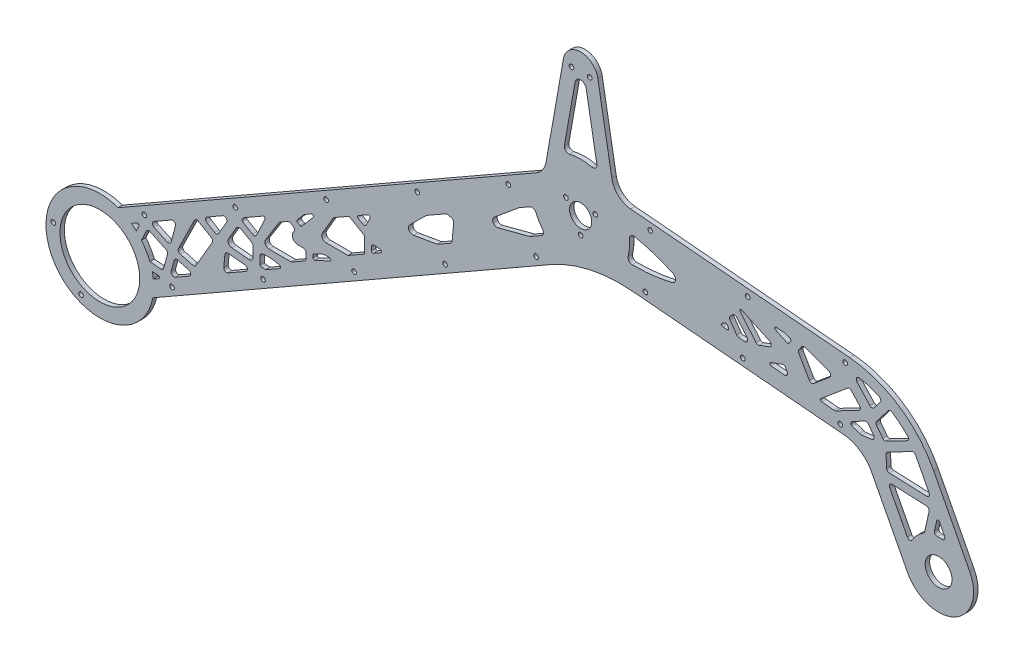
SolidWorks part; units mm, degrees
material "6061-T6 (SS)"
ref_plane "Front Plane" through (0, 0, 0) normal (0, 0, 1) x (1, 0, 0)
ref_plane "Top Plane" through (0, 0, 0) normal (0, 1, 0) x (1, 0, 0)
ref_plane "Right Plane" through (0, 0, 0) normal (1, 0, 0) x (0, 0, -1)
sketch "Reference Sketch" plane through (0, 0, 0) normal (0, 0, 1) x (1, 0, 0)
  line L0 (-343.92, -196.825) -> (0, 0) construction
  line L1 (-243.92, 103.175) -> (356.08, 103.175) construction
  line L2 (-243.92, 103.175) -> (-243.92, 0) construction
  line L3 (-243.92, 0) -> (356.08, 0) construction
  line L4 (356.08, 103.175) -> (356.08, 0) construction
  line L5 (0, 0) -> (256.08, -92.7116) construction
  line L6 (256.08, -92.7116) -> (56.08, -196.825) construction
  line L7 (256.08, -92.7116) -> (456.08, -196.825) construction
  line L8 (-343.92, -196.825) -> (56.08, -196.825) construction
  line L9 (56.08, -196.825) -> (456.08, -196.825) construction
  circle A1 centre (-343.92, -196.825) radius 100 construction
  circle A2 centre (56.08, -196.825) radius 100 construction
  circle A3 centre (456.08, -196.825) radius 100 construction
  circle A4 centre (-343.92, -196.825) radius 16.05 construction
  circle A5 centre (-343.92, -196.825) radius 28.55 construction
  circle A6 centre (-343.92, -196.825) radius 38.55 construction
  circle A7 centre (-343.92, -196.825) radius 33.55 construction
  point P13 (-343.92, -296.825)
  point P14 (556.08, -196.825)
  point P17 (-443.92, -196.825)
  dimension "D3" = 32.1
  dimension "D5" = 200
  dimension "D9" = 57.1
  dimension "D10" = 10
  dimension "D11" = 5
  dimension "D1" = 600
  dimension "D2" = 103.175
  dimension "D4" = 243.92
  dimension "D6" = 125
  dimension "D7" = 400
  dimension "D8" = 1000
sketch "Sketch2" plane through (0, 0, 0) normal (0, 0, 1) x (1, 0, 0)
  line L0 (-379.7168, -188.5069) -> (-32.0065, 10.4873)
  line L1 (-354.8814, -231.9028) -> (-21.5627, -41.1449)
  line L2 (-343.92, -196.825) -> (0, 0) construction
  line L3 (-184.3777, -76.7146) -> (-159.5423, -120.1104) construction
  line L4 (-24.685, 20.9013) -> (-12.3101, 91.0831)
  line L5 (12.3101, 91.0831) -> (22.322, 34.3028)
  line L6 (0, 98.4125) -> (0, 112.7) construction
  line L7 (-5.4848, 79.4125) -> (5.4848, 79.4125) construction
  line L8 (5.4848, 79.4125) -> (10.9697, 88.9125) construction
  line L9 (10.9697, 88.9125) -> (5.4848, 98.4125) construction
  line L10 (5.4848, 98.4125) -> (-5.4848, 98.4125) construction
  line L11 (-5.4848, 98.4125) -> (-10.9697, 88.9125) construction
  line L12 (-10.9697, 88.9125) -> (-5.4848, 79.4125) construction
  line L13 (-243.92, 103.175) -> (356.08, 103.175) construction
  line L14 (0, 88.9125) -> (0, 0) construction
  line L15 (35.7868, 21.9646) -> (192.5861, 8.2464)
  line L16 (252.5753, -31.8371) -> (278.2553, -81.1679)
  line L17 (233.9047, -104.2553) -> (208.2247, -54.9245)
  line L18 (36.8237, -28.3172) -> (188.2284, -41.5633)
  line L19 (0, 0) -> (192.5861, -16.8491) construction
  line L21 (-365.6311, -190.9191) -> (-338.0141, -175.1139) construction
  line L22 (-381.5729, -195.33) -> (-361.7045, -230.0467)
  line L23 (256.08, -92.7116) -> (56.08, -196.825) construction
  line L25 (-243.92, 0) -> (356.08, 0) construction
  circle A0 centre (0, 0) radius 7.9375
  circle A1 centre (-343.92, -196.825) radius 16.05
  arc A3 (-12.3101, 91.0831) -> (12.3101, 91.0831) centre (0, 88.9125) cw
  circle A4 centre (0, 88.9125) radius 6.5 construction
  circle A5 centre (-6.5, 88.9125) radius 1.65
  circle A6 centre (6.5, 88.9125) radius 1.65
  circle A7 centre (0, 88.9125) radius 9.5 construction
  arc A8 (252.5753, -31.8371) -> (192.5861, 8.2464) centre (186.0495, -66.4682) ccw
  circle A9 centre (256.08, -92.7116) radius 9.5885
  arc A10 (278.2553, -81.1679) -> (233.9047, -104.2553) centre (256.08, -92.7116) cw
  arc A11 (-21.5627, -41.1449) -> (36.8237, -28.3172) centre (28.1082, -127.9366) cw
  arc A12 (188.2284, -41.5633) -> (208.2247, -54.9245) centre (186.0495, -66.4682) cw
  arc A13 (22.322, 34.3028) -> (35.7868, 21.9646) centre (37.0941, 36.9075) ccw
  arc A14 (-32.0065, 10.4873) -> (-24.685, 20.9013) centre (-39.4572, 23.506) ccw
  circle A17 centre (-343.92, -196.825) radius 22.5 construction
  circle A18 centre (-365.6311, -190.9191) radius 1.65
  circle A19 centre (-338.0141, -175.1139) radius 1.65
  circle A20 centre (-322.2089, -202.7309) radius 1.65
  circle A21 centre (-349.8259, -218.5361) radius 1.65
  arc A27 (-379.7168, -188.5069) -> (-381.5729, -195.33) centre (-377.2333, -192.8465) ccw
  arc A28 (-361.7045, -230.0467) -> (-354.8814, -231.9028) centre (-357.3649, -227.5632) ccw
  circle A29 centre (-343.92, -196.825) radius 33.55 construction
  circle A32 centre (-343.92, -196.825) radius 38.55 construction
  point P16 (-171.96, -98.4125)
  point P64 (-343.92, -196.825)
  dimension "D1" = 15.875
  dimension "D2" = 32.1
  dimension "D3" = 45
  dimension "D5" = 13
  dimension "D6" = 3.3
  dimension "D7" = 6
  dimension "D12" = 50
  dimension "D14" = 100
  dimension "D16" = 15
  dimension "D17" = 5
  dimension "D18" = 25
  dimension "D19" = 3.3
  dimension "D15" = 4
  dimension "D20" = 19.177
  dimension "D4" = 50
  dimension "D8" = 19
  dimension "D9" = 14.2875
  dimension "D10" = 9.525
  dimension "D11" = 10
  dimension "D13" = 50
extrude "Base" add sketch "Sketch2" along normal blind 3.175
sketch "Sketch3" plane through (0, 0, 3.175) normal (0, 0, 1) x (1, 0, 0)
  line L0 (-343.92, -196.825) -> (0, 0) construction
  line L5 (0, 0) -> (197.3986, -17.2701) construction
  line L6 (192.5861, 8.2464) -> (35.7868, 21.9646) construction
  line L9 (36.8237, -28.3172) -> (188.2284, -41.5633) construction
  line L10 (-31.8958, -41.2976) -> (0, 0) construction
  line L11 (0, 0) -> (46.2693, -24.1244) construction
  circle A0 centre (-357.3649, -227.5632) radius 1.65
  circle A1 centre (-343.92, -196.825) radius 33.55 construction
  arc A2 (-361.7045, -230.0467) -> (-354.8814, -231.9028) centre (-357.3649, -227.5632) ccw construction
  circle A3 centre (-292.2711, -190.3101) radius 1.65
  circle A4 centre (-227.1773, -153.057) radius 1.65
  circle A5 centre (-162.0835, -115.8038) radius 1.65
  circle A6 centre (-96.9897, -78.5507) radius 1.65
  circle A7 centre (-31.8958, -41.2976) radius 1.65
  circle A8 centre (-312.1394, -155.5934) radius 1.65
  circle A9 centre (-377.2333, -192.8465) radius 1.65
  circle A10 centre (-247.0456, -118.3403) radius 1.65
  circle A11 centre (-181.9518, -81.0871) radius 1.65
  circle A12 centre (-116.858, -43.834) radius 1.65
  circle A13 centre (-51.7642, -6.5809) radius 1.65
  circle A14 centre (46.2693, -24.1244) radius 1.65
  circle A15 centre (116.0029, -30.2253) radius 1.65
  circle A16 centre (185.7366, -36.3262) radius 1.65
  circle A17 centre (189.2228, 3.5215) radius 1.65
  circle A18 centre (119.4892, 9.6224) radius 1.65
  circle A19 centre (49.7555, 15.7234) radius 1.65
  dimension "D1" = 3.3
  dimension "D2" = 6
  dimension "D3" = 5
  dimension "D5" = 3
  dimension "D4" = 75
  dimension "D6" = 70
extrude "Strut Holes" cut sketch "Sketch3" against normal through all
sketch "Sketch6" plane through (0, 0, 3.175) normal (0, 0, 1) x (1, 0, 0)
  line L0 (-315.2692, -197.7109) -> (-301.7593, -189.9792)
  line L1 (-354.8814, -231.9028) -> (-21.5627, -41.1449) construction
  line L2 (-289.845, -183.1607) -> (-279.9388, -177.4914)
  line L3 (-225.0683, -146.089) -> (-215.0659, -140.3647)
  line L4 (-202.4189, -105.5114) -> (-200.6862, -106.5205)
  line L5 (-330.4255, -170.6672) -> (-317.3783, -163.2003)
  line L6 (-32.0065, 10.4873) -> (-379.7168, -188.5069) construction
  line L7 (-315.9769, -164.4942) -> (-323.4022, -180.2613)
  line L8 (-325.3934, -181.4009) -> (-327.8261, -181.1787)
  line L9 (-302.165, -188.1154) -> (-317.5291, -186.7124)
  line L10 (-319.5204, -187.852) -> (-321.9207, -192.9489)
  line L11 (-295.5333, -171.6316) -> (-298.2962, -181.7883)
  line L12 (-300.4079, -183.2551) -> (-315.6625, -181.8621)
  line L13 (-317.2901, -179.0183) -> (-310.6415, -164.9005)
  line L14 (-307.9799, -163.9432) -> (-296.6111, -169.2972)
  line L15 (-280.4073, -173.8257) -> (-288.2923, -171.6808)
  line L16 (-290.7472, -173.0857) -> (-292.8686, -180.8843)
  line L17 (-292.7787, -149.122) -> (-305.2156, -156.2396)
  line L18 (-305.0743, -159.7848) -> (-295.766, -164.1685)
  line L19 (-292.984, -162.8841) -> (-289.8554, -151.3828)
  line L20 (-286.4122, -167.0105) -> (-277.4777, -169.4409)
  line L21 (-275.2245, -168.5176) -> (-263.487, -148.3649)
  line L22 (-264.2087, -145.6301) -> (-273.4911, -140.2238)
  line L23 (-276.2919, -141.0684) -> (-287.6814, -164.1971)
  line L24 (-267.3269, -134.556) -> (-255.9817, -128.0631)
  line L25 (-253.26, -130.8055) -> (-258.9575, -140.5878)
  line L26 (-261.6923, -141.3094) -> (-267.3401, -138.02)
  line L27 (-255.2613, -159.7424) -> (-254.4886, -151.2802)
  line L28 (-252.315, -149.4703) -> (-240.2297, -150.5739)
  line L29 (-292.2711, -190.3101) -> (-299.0066, -188.4038) construction
  line L30 (-252.2762, -161.6601) -> (-239.4181, -154.3014)
  line L31 (-246.5402, -131.1894) -> (-251.7948, -140.2114)
  line L32 (-249.4752, -144.7088) -> (-237.508, -145.8016)
  line L33 (-234.2352, -142.8254) -> (-234.2117, -136.6339)
  line L34 (-235.7018, -134.0302) -> (-242.4379, -130.1069)
  line L35 (-229.2226, -139.4963) -> (-229.2439, -145.1246)
  line L36 (-241.7536, -124.7193) -> (-234.6398, -128.8625)
  line L37 (-231.8238, -127.9864) -> (-225.7969, -115.1887)
  line L38 (-227.1983, -113.8948) -> (-240.4869, -121.4998)
  line L39 (-215.6688, -112.1749) -> (-225.38, -127.5855)
  line L40 (-222.8533, -132.1849) -> (-207.4544, -132.2434)
  line L41 (-206.4534, -131.9792) -> (-197.5057, -126.8584)
  line L42 (-196.4991, -125.1302) -> (-196.4845, -121.2849)
  line L43 (-198.4769, -119.2773) -> (-202.2607, -119.2629)
  line L44 (-205.6297, -113.1304) -> (-205.0269, -112.1739)
  line L45 (-205.7124, -109.3794) -> (-207.4618, -108.3605)
  line L46 (-209.4618, -108.3529) -> (-214.9702, -111.5053)
  line L47 (-223.2993, -137.1832) -> (-189.5978, -137.3112) construction
  line L48 (-199.4194, -106.3021) -> (-191.3609, -96.7721)
  line L49 (-192.6212, -95.2585) -> (-197.479, -98.0386)
  line L50 (-198.0128, -98.4831) -> (-202.6792, -104.0016)
  line L51 (-191.4798, -120.0542) -> (-191.4866, -121.8475)
  line L52 (-190.0674, -122.7592) -> (-179.2455, -117.7628)
  line L54 (-190.899, -119.1501) -> (-184.1308, -116.0253)
  line L55 (-183.2849, -115.8411) -> (-179.6609, -115.8549)
  line L56 (-166.4011, -107.9052) -> (-182.2049, -107.8452)
  line L57 (-184.7858, -103.3353) -> (-176.832, -89.6789)
  line L58 (-176.832, -89.6789) -> (-165.639, -83.2731)
  line L59 (-165.639, -83.2731) -> (-154.6405, -89.6789)
  line L60 (-154.6405, -89.6789) -> (-154.6842, -101.1996)
  line L61 (-154.6842, -101.1996) -> (-166.4011, -107.9052)
  line L62 (-176.832, -89.6789) -> (-166.4011, -107.9052) construction
  line L63 (-149.6667, -96.5998) -> (-149.6576, -94.1811)
  line L64 (-147.4757, -92.197) -> (-143.2847, -92.5797)
  line L65 (-142.8789, -94.4434) -> (-148.17, -97.4715)
  line L66 (-159.1247, -79.5451) -> (-152.014, -75.4756)
  line L67 (-150.6126, -76.7696) -> (-153.1821, -82.2258)
  line L68 (-155.9981, -83.102) -> (-159.1313, -81.2771)
  line L69 (-154.1121, -84.2004) -> (-149.6493, -91.9985) construction
  line L70 (-90.8199, -49.6985) -> (-91.8964, -61.4879)
  line L71 (-93.3939, -63.8188) -> (-101.9943, -68.7409)
  line L72 (-102.9747, -69.0935) -> (-119.6299, -71.9651)
  line L73 (-122.2529, -66.8794) -> (-110.6811, -55.3952)
  line L74 (-110.058, -54.9208) -> (-96.7247, -47.2901)
  line L75 (-94.4471, -46.9991) -> (-92.2866, -47.5868)
  line L76 (-102.4534, -69.0036) -> (-110.4008, -55.117) construction
  line L78 (-28.0968, -26.4494) -> (-35.8254, -30.8725)
  line L79 (-36.5501, -31.1694) -> (-59.134, -37.129)
  line L80 (-61.819, -31.9228) -> (-44.3172, -17.3499)
  line L81 (-43.8877, -17.0516) -> (-36.2746, -12.6946)
  line L82 (-44.1155, -17.182) -> (-36.1682, -31.0687) construction
  line L83 (-11.5997, 37.5245) -> (-3.9861, 80.7029)
  line L84 (3.9861, 80.7029) -> (11.5997, 37.5245)
  line L85 (22.322, 34.3028) -> (12.3101, 91.0831) construction
  line L86 (-12.3101, 91.0831) -> (-24.685, 20.9013) construction
  line L87 (192.5861, 8.2464) -> (35.7868, 21.9646) construction
  line L88 (36.8237, -28.3172) -> (188.2284, -41.5633) construction
  line L89 (-227.1773, -153.057) -> (-233.9128, -151.1507) construction
  line L90 (246.076, -72.9136) -> (249.254, -58.5784)
  line L91 (247.3887, -56.1475) -> (222.9622, -55.081)
  line L92 (221.1009, -58.0026) -> (233.7353, -82.273)
  line L93 (208.2247, -54.9245) -> (233.9047, -104.2553) construction
  line L94 (253.1337, -68.7997) -> (254.752, -61.5)
  line L95 (256.6153, -61.2547) -> (260.3456, -68.4206)
  line L96 (278.2553, -81.1679) -> (252.5753, -31.8371) construction
  line L97 (249.3108, -47.2228) -> (239.5975, -28.5637)
  line L98 (236.9, -27.7132) -> (219.5656, -36.7369)
  line L99 (218.491, -38.5982) -> (218.8608, -47.0688)
  line L100 (220.7717, -48.9796) -> (247.4495, -50.1444)
  line L101 (233.4135, -22.7639) -> (218.6181, -30.4658)
  line L102 (216.1079, -29.9093) -> (211.6718, -24.1281)
  line L103 (211.6718, -21.693) -> (220.0072, -10.8302)
  line L104 (209.6166, -31.3057) -> (205.7463, -26.2618)
  line L105 (203.2361, -25.7053) -> (194.0101, -30.5081)
  line L106 (193.4718, -31.3951) -> (193.4718, -32.4967)
  line L107 (201.069, -35.4569) -> (208.2909, -34.5061)
  line L108 (214.3031, -8.4078) -> (209.9577, -14.0708)
  line L109 (197.6887, -4.156) -> (206.8964, -14.2045)
  line L110 (193.6814, -11.6243) -> (199.5455, -18.0239)
  line L111 (198.9945, -21.1491) -> (182.8075, -29.5754)
  line L112 (181.1608, -29.903) -> (172.4826, -29.1438)
  line L113 (171.927, -27.3815) -> (190.9213, -11.4434)
  line L114 (178.1992, -11.0225) -> (166.5918, -20.7623)
  line L115 (163.5742, -20.2302) -> (156.048, -7.1944)
  line L116 (156.1417, -5.0472) -> (158.1885, -2.1242)
  line L117 (160.5108, -1.3919) -> (177.5977, -7.611)
  line L118 (146.6448, -20.9077) -> (147.747, -22.8167)
  line L119 (145.8406, -25.8091) -> (136.23, -24.9682)
  line L120 (135.9751, -23.0324) -> (144.2287, -20.0283)
  line L121 (134.9743, -13.819) -> (127.6718, -16.4769)
  line L122 (125.4557, -15.8831) -> (114.1985, -2.4673)
  line L123 (115.3872, -0.9182) -> (135.1355, -10.127)
  line L124 (139.4306, -1.096) -> (147.8318, -5.0136)
  line L125 (149.0736, -4.6809) -> (150.4259, -2.7496)
  line L126 (149.9488, -1.2363) -> (146.0985, 0.1651)
  line L127 (145.3339, 0.3346) -> (139.9404, 0.8065)
  line L128 (111.6605, -7.2212) -> (119.0455, -16.0223)
  line L129 (117.3391, -19.3002) -> (113.1162, -18.9308)
  line L130 (111.6522, -18.0855) -> (106.8775, -11.2665)
  line L131 (107.1016, -8.7052) -> (108.7142, -7.0926)
  line L132 (104.7039, -15.1361) -> (105.7554, -16.6377)
  line L133 (104.8491, -18.2075) -> (101.6773, -17.93)
  line L134 (101.2644, -16.0678) -> (103.3847, -14.8436)
  arc A0 (-317.584, -197.4764) -> (-320.5599, -195.9279) centre (-322.2089, -202.7309) ccw
  arc A1 (-291.1568, -183.3993) -> (-291.2348, -183.3872) centre (-292.2711, -190.3101) ccw
  arc A2 (-225.7665, -146.2006) -> (-228.1106, -146.1195) centre (-227.1773, -153.057) ccw
  arc A4 (-322.0747, -194.2209) -> (-322.0953, -194.053) centre (-343.92, -196.825) ccw
  arc A5 (-331.3132, -177.1382) -> (-331.3392, -173.0054) centre (-338.0141, -175.1139) ccw
  arc A6 (-329.0005, -180.6569) -> (-330.6088, -179.309) centre (-343.92, -196.825) ccw
  arc A8 (-227.5555, -137.5318) -> (-215.2363, -138.5515) centre (-223.3943, -162.1831) cw
  arc A9 (-241.9747, -123.1658) -> (-241.1717, -122.1478) centre (-247.0456, -118.3403) ccw
  arc A10 (-32.0383, -14.0906) -> (-27.2511, -21.9631) centre (0, 0) ccw
  arc A11 (-251.7948, -140.2114) -> (-249.4752, -144.7088) centre (-249.2024, -141.7213) ccw
  arc A12 (-225.38, -127.5855) -> (-222.8533, -132.1849) centre (-222.8419, -129.1849) ccw
  arc A13 (-182.2049, -107.8452) -> (-184.7858, -103.3353) centre (-182.1935, -104.8452) cw
  arc A14 (-119.6299, -71.9651) -> (-122.2529, -66.8794) centre (-120.1396, -69.0087) cw
  arc A15 (-59.134, -37.129) -> (-61.819, -31.9228) centre (-59.8994, -34.2283) cw
  arc A16 (-7.9627, 34.0822) -> (7.9627, 34.0822) centre (0, 0) cw
  arc A17 (-3.9861, 80.7029) -> (3.9861, 80.7029) centre (0, 80) cw
  arc A18 (34.8636, 3.0867) -> (34.0029, -8.2948) centre (0, 0) cw
  arc A19 (38.4335, 6.2944) -> (66.0977, -2.7713) centre (15.1723, -111.4295) cw
  arc A20 (66.0977, -2.7713) -> (65.4856, -8.7407) centre (64.749, -5.6491) cw
  arc A21 (36.898, -12.0057) -> (65.4856, -8.7407) centre (37.6733, 107.9918) ccw
  arc A22 (245.141, -74.2025) -> (237.26, -82.3165) centre (256.08, -92.7116) ccw
  arc A23 (258.3595, -71.3328) -> (255.1708, -71.2308) centre (256.08, -92.7116) ccw
  arc A24 (222.6875, -10.3732) -> (233.9189, -19.5905) centre (186.0495, -66.4682) cw
  arc A25 (252.5753, -31.8371) -> (192.5861, 8.2464) centre (186.0495, -66.4682) ccw construction
  arc A26 (194.2312, -33.4673) -> (199.4914, -35.2382) centre (186.0495, -66.4682) cw
  arc A27 (208.2247, -54.9245) -> (188.2284, -41.5633) centre (186.0495, -66.4682) ccw construction
  arc A28 (213.5369, -5.3663) -> (199.5667, -0.8459) centre (186.0495, -66.4682) ccw
  arc A29 (218.8608, -47.0688) -> (220.7717, -48.9796) centre (220.8589, -46.9815) ccw
  arc A30 (239.5975, -28.5637) -> (236.9, -27.7132) centre (237.8235, -29.4872) ccw
  arc A31 (219.5656, -36.7369) -> (218.491, -38.5982) centre (220.4891, -38.5109) ccw
  arc A32 (127.6718, -16.4769) -> (125.4557, -15.8831) centre (126.9878, -14.5975) cw
  arc A33 (-240.4869, -121.4998) -> (-241.1717, -122.1478) centre (-239.4934, -123.2356) ccw
  arc A34 (-234.6398, -128.8625) -> (-231.8238, -127.9864) centre (-233.6332, -127.1343) ccw
  arc A35 (-229.2226, -139.4963) -> (-227.5555, -137.5318) centre (-227.2226, -139.5039) cw
  arc A36 (-315.2692, -197.7109) -> (-317.584, -197.4764) centre (-316.2626, -195.9751) cw
  arc A37 (-322.0747, -194.2209) -> (-320.5599, -195.9279) centre (-320.0887, -193.9842) ccw
  arc A38 (-321.9207, -192.9489) -> (-322.0953, -194.053) centre (-320.1113, -193.801) ccw
  arc A39 (-317.5291, -186.7124) -> (-319.5204, -187.852) centre (-317.711, -188.7042) ccw
  arc A40 (-323.4022, -180.2613) -> (-325.3934, -181.4009) centre (-325.2116, -179.4092) cw
  arc A41 (-327.8261, -181.1787) -> (-329.0005, -180.6569) centre (-327.6442, -179.187) cw
  arc A42 (-331.3132, -177.1382) -> (-330.6088, -179.309) centre (-329.3986, -177.7166) ccw
  arc A43 (-330.4255, -170.6672) -> (-331.3392, -173.0054) centre (-329.4321, -172.403) ccw
  arc A44 (-315.6625, -181.8621) -> (-317.2901, -179.0183) centre (-315.4807, -179.8704) cw
  arc A45 (-298.2962, -181.7883) -> (-300.4079, -183.2551) centre (-300.226, -181.2634) cw
  arc A46 (-289.845, -183.1607) -> (-291.1568, -183.3993) centre (-290.8384, -181.4248) cw
  arc A47 (-292.8686, -180.8843) -> (-291.2348, -183.3872) centre (-290.9387, -181.4092) ccw
  arc A48 (-280.4073, -173.8257) -> (-279.9388, -177.4914) centre (-280.9322, -175.7556) cw
  arc A49 (-288.2923, -171.6808) -> (-290.7472, -173.0857) centre (-288.8173, -173.6107) ccw
  arc A50 (-295.5333, -171.6316) -> (-296.6111, -169.2972) centre (-297.4632, -171.1066) ccw
  arc A51 (-310.6415, -164.9005) -> (-307.9799, -163.9432) centre (-308.8321, -165.7526) cw
  arc A52 (-305.2156, -156.2396) -> (-305.0743, -159.7848) centre (-304.2222, -157.9754) ccw
  arc A53 (-292.7787, -149.122) -> (-289.8554, -151.3828) centre (-291.7853, -150.8578) cw
  arc A54 (-295.766, -164.1685) -> (-292.984, -162.8841) centre (-294.9139, -162.3591) ccw
  arc A55 (-286.4122, -167.0105) -> (-287.6814, -164.1971) centre (-285.8872, -165.0807) cw
  arc A56 (-277.4777, -169.4409) -> (-275.2245, -168.5176) centre (-276.9527, -167.511) ccw
  arc A57 (-263.487, -148.3649) -> (-264.2087, -145.6301) centre (-265.2153, -147.3583) ccw
  arc A58 (-273.4911, -140.2238) -> (-276.2919, -141.0684) centre (-274.4977, -141.952) ccw
  arc A59 (-267.3269, -134.556) -> (-267.3401, -138.02) centre (-266.3335, -136.2918) ccw
  arc A60 (-258.9575, -140.5878) -> (-261.6923, -141.3094) centre (-260.6857, -139.5812) cw
  arc A61 (-254.4886, -151.2802) -> (-252.315, -149.4703) centre (-252.4969, -151.462) cw
  arc A62 (-255.2613, -159.7424) -> (-252.2762, -161.6601) centre (-253.2696, -159.9243) ccw
  arc A63 (-239.4181, -154.3014) -> (-240.2297, -150.5739) centre (-240.4115, -152.5656) ccw
  arc A64 (-255.9817, -128.0631) -> (-253.26, -130.8055) centre (-254.9883, -129.7989) cw
  arc A65 (-207.4544, -132.2434) -> (-206.4534, -131.9792) centre (-207.4468, -130.2434) ccw
  arc A66 (-214.9702, -111.5053) -> (-215.6688, -112.1749) centre (-213.9767, -113.2412) ccw
  arc A67 (-207.4618, -108.3605) -> (-209.4618, -108.3529) centre (-208.4684, -110.0887) ccw
  arc A68 (-205.0269, -112.1739) -> (-205.7124, -109.3794) centre (-206.719, -111.1076) ccw
  arc A69 (-202.2607, -119.2629) -> (-205.6297, -113.1304) centre (-202.2456, -115.263) cw
  arc A70 (-196.4845, -121.2849) -> (-198.4769, -119.2773) centre (-198.4845, -121.2773) ccw
  arc A71 (-197.5057, -126.8584) -> (-196.4991, -125.1302) centre (-198.4991, -125.1226) ccw
  arc A72 (-184.1308, -116.0253) -> (-183.2849, -115.8411) centre (-183.2925, -117.8411) cw
  arc A73 (-197.479, -98.0386) -> (-198.0128, -98.4831) centre (-196.4856, -99.7744) ccw
  arc A74 (-149.6576, -94.1811) -> (-147.4757, -92.197) centre (-147.6576, -94.1887) cw
  arc A75 (-153.1821, -82.2258) -> (-155.9981, -83.102) centre (-154.9915, -81.3737) cw
  arc A76 (-90.8199, -49.6985) -> (-92.2866, -47.5868) centre (-92.8116, -49.5167) ccw
  arc A77 (111.6605, -7.2212) -> (108.7142, -7.0926) centre (110.1284, -8.5068) ccw
  arc A78 (106.8775, -11.2665) -> (107.1016, -8.7052) centre (108.5158, -10.1194) cw
  arc A79 (113.1162, -18.9308) -> (111.6522, -18.0855) centre (113.2905, -16.9384) cw
  arc A80 (119.0455, -16.0223) -> (117.3391, -19.3002) centre (117.5134, -17.3078) cw
  arc A81 (134.9743, -13.819) -> (135.1355, -10.127) centre (134.2903, -11.9396) ccw
  arc A82 (146.6448, -20.9077) -> (144.2287, -20.0283) centre (144.9128, -21.9077) ccw
  arc A83 (147.747, -22.8167) -> (145.8406, -25.8091) centre (146.0149, -23.8167) cw
  arc A84 (156.048, -7.1944) -> (156.1417, -5.0472) centre (157.78, -6.1944) cw
  arc A85 (158.1885, -2.1242) -> (160.5108, -1.3919) centre (159.8268, -3.2713) cw
  arc A86 (178.1992, -11.0225) -> (177.5977, -7.611) centre (176.9136, -9.4904) ccw
  arc A87 (166.5918, -20.7623) -> (163.5742, -20.2302) centre (165.3062, -19.2302) cw
  arc A88 (193.6814, -11.6243) -> (190.9213, -11.4434) centre (192.2068, -12.9755) ccw
  arc A89 (199.5455, -18.0239) -> (198.9945, -21.1491) centre (198.071, -19.375) cw
  arc A90 (209.9577, -14.0708) -> (206.8964, -14.2045) centre (208.371, -12.8533) cw
  arc A91 (213.5369, -5.3663) -> (214.3031, -8.4078) centre (212.7164, -7.1903) cw
  arc A92 (233.9189, -19.5905) -> (233.4135, -22.7639) centre (232.49, -20.9899) cw
  arc A93 (222.6875, -10.3732) -> (220.0072, -10.8302) centre (221.5939, -12.0477) ccw
  arc A94 (211.6718, -24.1281) -> (211.6718, -21.693) centre (213.2585, -22.9105) cw
  arc A95 (218.6181, -30.4658) -> (216.1079, -29.9093) centre (217.6946, -28.6918) cw
  arc A96 (205.7463, -26.2618) -> (203.2361, -25.7053) centre (204.1595, -27.4793) ccw
  arc A97 (209.6166, -31.3057) -> (208.2909, -34.5061) centre (208.0299, -32.5232) cw
  arc A98 (246.076, -72.9136) -> (245.141, -74.2025) centre (244.1234, -72.4807) cw
  arc A99 (249.254, -58.5784) -> (247.3887, -56.1475) centre (247.3014, -58.1456) ccw
  arc A100 (222.9622, -55.081) -> (221.1009, -58.0026) centre (222.8749, -57.0791) ccw
  arc A101 (233.7353, -82.273) -> (237.26, -82.3165) centre (235.5093, -81.3495) ccw
  arc A102 (260.3456, -68.4206) -> (258.3595, -71.3328) centre (258.5716, -69.344) cw
  arc A103 (253.1337, -68.7997) -> (255.1708, -71.2308) centre (255.0863, -69.2326) ccw
  arc A104 (249.3108, -47.2228) -> (247.4495, -50.1444) centre (247.5367, -48.1463) cw
  arc A105 (199.5667, -0.8459) -> (197.6887, -4.156) centre (199.1632, -2.8048) ccw
  arc A106 (-215.2363, -138.5515) -> (-215.0659, -140.3647) centre (-215.5626, -139.4968) cw
  arc A107 (-301.7593, -189.9792) -> (-302.165, -188.1154) centre (-302.256, -189.1113) ccw
  arc A108 (-317.3783, -163.2003) -> (-315.9769, -164.4942) centre (-316.8815, -164.0682) cw
  arc A109 (-225.7969, -115.1887) -> (-227.1983, -113.8948) centre (-226.7016, -114.7627) ccw
  arc A110 (-241.7536, -124.7193) -> (-241.9747, -123.1658) centre (-241.2503, -123.8551) cw
  arc A111 (-225.7665, -146.2006) -> (-225.0683, -146.089) centre (-225.565, -145.2211) ccw
  arc A112 (-229.2439, -145.1246) -> (-228.1106, -146.1195) centre (-228.2439, -145.1284) ccw
  arc A113 (-202.4189, -105.5114) -> (-202.6792, -104.0016) centre (-201.9156, -104.6473) cw
  arc A114 (-200.6862, -106.5205) -> (-199.4194, -106.3021) centre (-200.183, -105.6564) ccw
  arc A115 (-191.4798, -120.0542) -> (-190.899, -119.1501) centre (-190.4798, -120.058) cw
  arc A116 (-191.4866, -121.8475) -> (-190.0674, -122.7592) centre (-190.4866, -121.8513) ccw
  arc A117 (-191.3609, -96.7721) -> (-192.6212, -95.2585) centre (-192.1245, -96.1264) ccw
  arc A118 (-179.2455, -117.7628) -> (-179.6609, -115.8549) centre (-179.6647, -116.8549) ccw
  arc A119 (-152.014, -75.4756) -> (-150.6126, -76.7696) centre (-151.5173, -76.3435) cw
  arc A120 (-159.1247, -79.5451) -> (-159.1313, -81.2771) centre (-158.628, -80.413) ccw
  arc A121 (-149.6667, -96.5998) -> (-148.17, -97.4715) centre (-148.6667, -96.6036) ccw
  arc A122 (-143.2847, -92.5797) -> (-142.8789, -94.4434) centre (-143.3756, -93.5755) cw
  arc A123 (101.6773, -17.93) -> (101.2644, -16.0678) centre (101.7644, -16.9338) cw
  arc A124 (104.7039, -15.1361) -> (103.3847, -14.8436) centre (103.8847, -15.7096) ccw
  arc A125 (105.7554, -16.6377) -> (104.8491, -18.2075) centre (104.9362, -17.2113) cw
  arc A126 (114.1985, -2.4673) -> (115.3872, -0.9182) centre (114.9646, -1.8245) cw
  arc A127 (136.23, -24.9682) -> (135.9751, -23.0324) centre (136.3171, -23.972) cw
  arc A128 (139.4306, -1.096) -> (139.9404, 0.8065) centre (139.8532, -0.1897) cw
  arc A129 (172.4826, -29.1438) -> (171.927, -27.3815) centre (172.5698, -28.1476) cw
  arc A130 (194.0101, -30.5081) -> (193.4718, -31.3951) centre (194.4718, -31.3951) ccw
  arc A131 (193.4718, -32.4967) -> (194.2312, -33.4673) centre (194.4718, -32.4967) ccw
  arc A132 (254.752, -61.5) -> (256.6153, -61.2547) centre (255.7283, -61.7164) cw
  arc A133 (146.0985, 0.1651) -> (145.3339, 0.3346) centre (145.0724, -2.654) ccw
  arc A134 (199.4914, -35.2382) -> (201.069, -35.4569) centre (200.6774, -32.4826) ccw
  arc A135 (182.8075, -29.5754) -> (181.1608, -29.903) centre (181.4223, -26.9144) cw
  arc A136 (-7.9627, 34.0822) -> (-11.5997, 37.5245) centre (-8.6452, 37.0035) cw
  arc A137 (7.9627, 34.0822) -> (11.5997, 37.5245) centre (8.6452, 37.0035) ccw
  arc A138 (34.8636, 3.0867) -> (38.4335, 6.2944) centre (37.8519, 3.3513) cw
  arc A139 (34.0029, -8.2948) -> (36.898, -12.0057) centre (36.9174, -9.0058) ccw
  arc A140 (-35.8254, -30.8725) -> (-36.5501, -31.1694) centre (-37.3155, -28.2687) cw
  arc A141 (-44.3172, -17.3499) -> (-43.8877, -17.0516) centre (-42.3976, -19.6554) cw
  arc A142 (-32.0383, -14.0906) -> (-36.2746, -12.6946) centre (-34.7845, -15.2984) ccw
  arc A143 (-27.2511, -21.9631) -> (-28.0968, -26.4494) centre (-29.5869, -23.8456) cw
  arc A144 (-96.7247, -47.2901) -> (-94.4471, -46.9991) centre (-95.2346, -49.8939) cw
  arc A145 (-91.8964, -61.4879) -> (-93.3939, -63.8188) centre (-94.884, -61.2151) cw
  arc A146 (-110.6811, -55.3952) -> (-110.058, -54.9208) centre (-108.5679, -57.5245) cw
  arc A147 (-101.9943, -68.7409) -> (-102.9747, -69.0935) centre (-103.4845, -66.1371) cw
  arc A148 (-246.5402, -131.1894) -> (-242.4379, -130.1069) centre (-243.9478, -132.6992) cw
  arc A149 (-234.2117, -136.6339) -> (-235.7018, -134.0302) centre (-237.2117, -136.6225) ccw
  arc A150 (-237.508, -145.8016) -> (-234.2352, -142.8254) centre (-237.2352, -142.8141) ccw
  arc A151 (150.4259, -2.7496) -> (149.9488, -1.2363) centre (149.6067, -2.176) ccw
  arc A152 (147.8318, -5.0136) -> (149.0736, -4.6809) centre (148.2544, -4.1073) ccw
  point P98 (-116.858, -43.834)
  point P110 (-254.1648, -144.2806)
  point P113 (-228.2654, -132.1643)
  point P143 (34.9003, -2.6394)
  point P203 (218.9408, -48.8997)
  point P206 (238.674, -26.7897)
  point P211 (126.3559, -16.9559)
  point P214 (-240.9361, -121.7569)
  point P217 (-232.7537, -129.961)
  point P220 (-229.2164, -137.8704)
  point P229 (-318.9237, -186.5851)
  point P232 (-323.9988, -181.5282)
  point P235 (-328.5183, -181.1155)
  point P240 (-331.9839, -171.5591)
  point P247 (-290.5028, -183.5371)
  point P252 (-275.7482, -175.0931)
  point P255 (-290.2222, -171.1558)
  point P262 (-308.5502, -158.1479)
  point P265 (-288.588, -146.7237)
  point P268 (-293.6097, -165.184)
  point P271 (-288.7533, -166.3737)
  point P278 (-275.3444, -139.1443)
  point P281 (-270.3335, -136.2766)
  point P288 (-255.6107, -163.5684)
  point P294 (-249.5035, -124.3556)
  point P297 (-206.9185, -132.2454)
  point P300 (-215.403, -111.753)
  point P303 (-208.4596, -107.7794)
  point P308 (-209.4769, -119.2355)
  point P311 (-196.4769, -119.2849)
  point P314 (-196.5035, -126.2849)
  point P329 (110.2575, -5.5492)
  point P334 (112.1872, -18.8495)
  point P337 (122.1491, -19.721)
  point P340 (139.5116, -12.1676)
  point P345 (149.6679, -26.1439)
  point P350 (159.0687, -0.8671)
  point P353 (180.8529, -8.7958)
  point P356 (164.7659, -22.2944)
  point P363 (208.5067, -15.9618)
  point P366 (215.8118, -6.4415)
  point P369 (235.7568, -21.544)
  point P374 (210.7376, -22.9105)
  point P377 (217.1296, -31.2407)
  point P380 (204.7246, -24.9304)
  point P383 (211.7254, -34.054)
  point P390 (219.5014, -54.9299)
  point P393 (235.6626, -85.9753)
  point P396 (262.2729, -72.1228)
  point P401 (250.9103, -50.2955)
  point P406 (-213.2581, -139.3301)
  point P412 (-314.6256, -161.6249)
  point P415 (-224.4456, -112.3194)
  point P420 (-225.4089, -146.284)
  point P423 (-229.2487, -146.3704)
  point P426 (-203.4487, -104.9116)
  point P431 (-191.4774, -119.4171)
  point P434 (-191.4925, -123.4171)
  point P437 (-187.699, -92.4415)
  point P440 (-175.1502, -115.872)
  point P447 (-149.6733, -98.3319)
  point P450 (-140.1262, -92.8681)
  point P453 (98.5177, -17.6536)
  point P458 (106.9854, -18.3944)
  point P463 (131.7364, -24.5751)
  point P468 (170.0776, -28.9333)
  point P471 (193.4718, -30.7883)
  point P474 (193.4718, -33.2883)
  point P477 (255.3467, -58.8176)
  point P484 (182.0319, -29.9792)
  point P491 (34.2849, 7.0387)
  point P494 (32.91, -11.9136)
  point P505 (-24.8853, -24.6115)
  point P508 (-95.6462, -46.6729)
  point P511 (-92.0384, -63.0431)
  point P524 (-234.2477, -146.0993)
  point P527 (151.1734, -1.682)
  point P530 (148.5923, -5.3682)
  dimension "D1" = 14
  dimension "D2" = 10
  dimension "D3" = 2
  dimension "D5" = 22
  dimension "D6" = 9
  dimension "D12" = 5
  dimension "D19" = 7
  dimension "D31" = 7
  dimension "D40" = 25
  dimension "D44" = 19
  dimension "D62" = 5
  dimension "D92" = 35
  dimension "D96" = 3
  dimension "D97" = 10
  dimension "D100" = 15
  dimension "D104" = 30
  dimension "D105" = 120
  dimension "D107" = 43
  dimension "D116" = 65
  dimension "D117" = 8
  dimension "D127" = 9
  dimension "D128" = 6
  dimension "D171" = 2
  dimension "D172" = 1
  dimension "D173" = 3
  dimension "D174" = 1
  dimension "D175" = 4
  dimension "D7" = 35
  dimension "D8" = 35
  dimension "D9" = 20
  dimension "D10" = 22
  dimension "D11" = 20
  dimension "D13" = 5
  dimension "D14" = 45
  dimension "D15" = 45
  dimension "D16" = 17
  dimension "D17" = 15
  dimension "D18" = 5
  dimension "D20" = 55
  dimension "D21" = 5
  dimension "D22" = 45
  dimension "D23" = 23
  dimension "D24" = 34
  dimension "D25" = 60
  dimension "D26" = 5
  dimension "D27" = 5
  dimension "D28" = 5
  dimension "D29" = 30
  dimension "D30" = 24
  dimension "D32" = 55
  dimension "D33" = 35
  dimension "D34" = 25
  dimension "D35" = 5
  dimension "D36" = 6
  dimension "D37" = 60
  dimension "D38" = 5
  dimension "D39" = 20
  dimension "D41" = 11
  dimension "D42" = 35
  dimension "D43" = 60
  dimension "D45" = 19.5
  dimension "D46" = 5
  dimension "D47" = 5
  dimension "D48" = 30
  dimension "D49" = 5
  dimension "D50" = 14
  dimension "D51" = 13
  dimension "D52" = 8.5
  dimension "D53" = 60
  dimension "D54" = 12
  dimension "D55" = 7
  dimension "D56" = 22
  dimension "D57" = 28
  dimension "D58" = 60
  dimension "D59" = 15
  dimension "D60" = 8
  dimension "D61" = 13
  dimension "D63" = 12
  dimension "D64" = 20
  dimension "D65" = 5
  dimension "D66" = 65
  dimension "D67" = 25
  dimension "2" = 18
  dimension "D68" = 8
  dimension "D69" = 4
  dimension "D70" = 14
  dimension "D71" = 15
  dimension "D72" = 13.5
  dimension "D73" = 60
  dimension "D74" = 60
  dimension "D75" = 8
  dimension "D76" = 5
  dimension "D77" = 35
  dimension "D78" = 0.5076
  dimension "D79" = 5
  dimension "D80" = 11
  dimension "D81" = 35
  dimension "D82" = 16
  dimension "D83" = 18
  dimension "D84" = 55
  dimension "D85" = 45
  dimension "D86" = 20
  dimension "D87" = 15
  dimension "D88" = 12
  dimension "D89" = 17
  dimension "D90" = 16
  dimension "D91" = 18
  dimension "D93" = 15
  dimension "D94" = 10
  dimension "D95" = 13
  dimension "D98" = 10
  dimension "D99" = 80
  dimension "D101" = 16
  dimension "D102" = 22
  dimension "D103" = 22
  dimension "D106" = 7
  dimension "D108" = 10
  dimension "D109" = 40
  dimension "D110" = 10
  dimension "D111" = 6
  dimension "D112" = 60
  dimension "D113" = 35
  dimension "D114" = 15
  dimension "D115" = 6
  dimension "D118" = 26.5
  dimension "D119" = 6
  dimension "D120" = 85
  dimension "D121" = 85
  dimension "D122" = 32
  dimension "D123" = 21
  dimension "D124" = 80
  dimension "D125" = 75
  dimension "D126" = 6
  dimension "D129" = 10.5
  dimension "D130" = 80
  dimension "D131" = 12
  dimension "D132" = 8
  dimension "D133" = 6
  dimension "D134" = 2.5
  dimension "D135" = 100
  dimension "D136" = 11.5
  dimension "D137" = 60
  dimension "D138" = 11
  dimension "D139" = 45
  dimension "D140" = 12
  dimension "D141" = 8.5
  dimension "D142" = 12
  dimension "D143" = 18
  dimension "D144" = 80
  dimension "D145" = 21
  dimension "D146" = 60
  dimension "D147" = 60
  dimension "D148" = 15
  dimension "D149" = 12
  dimension "D150" = 18
  dimension "D151" = 25
  dimension "D152" = 9
  dimension "D153" = 12
  dimension "D154" = 6
  dimension "D155" = 15
  dimension "D156" = 20
  dimension "D157" = 10
  dimension "D158" = 13.5
  dimension "D159" = 4.5
  dimension "D160" = 45
  dimension "D161" = 14
  dimension "D162" = 5
  dimension "D163" = 10
  dimension "D164" = 16
  dimension "D165" = 50
  dimension "D166" = 18.5
  dimension "D167" = 50
  dimension "D168" = 4
  dimension "D169" = 8.5
  dimension "D170" = 35
extrude "Lightening Holes" cut sketch "Sketch6" against normal through all
sketch "Sketch7" plane through (0, 0, 3.175) normal (0, 0, 1) x (1, 0, 0)
  circle A13 centre (-357.3649, -227.5632) radius 1.65 construction
  circle A15 centre (-377.2333, -192.8465) radius 1.65 construction
  circle A16 centre (-343.92, -196.825) radius 38.55 construction
  circle A17 centre (-343.92, -196.825) radius 28.55 construction
  circle A26 centre (-357.3649, -227.5632) radius 1.65
  circle A27 centre (-377.2333, -192.8465) radius 1.65
  circle A28 centre (-343.92, -196.825) radius 38.55
  circle A29 centre (-343.92, -196.825) radius 28.55
extrude "Inner Mod Extrusion" add sketch "Sketch7" against normal up to surface (3.175 mm away) up to face at (-260.7262, -135.4767, 0)
extrude "Inner Mod Cut" cut sketch "Sketch7<2>" against normal through all contours A29 region at (-343.92, -196.825, 3.175)
sketch "Sketch7<2>" plane through (0, 0, 3.175) normal (0, 0, 1) x (1, 0, 0) same geometry as "Sketch7"
sketch "Sketch8" plane through (0, 0, 3.175) normal (0, 0, 1) x (1, 0, 0)
  circle A0 centre (-10.5, 6.0622) radius 1.65
  circle A1 centre (10.5, 6.0622) radius 1.65
  circle A2 centre (0, -12.1244) radius 1.65
  point P0 (0, 0)
  point P1 (0, 0)
  point P14 (0, 0)
  dimension "D2" = 3.3
  dimension "D1" = 21
  dimension "D3" = 3
extrude "Cut-Extrude1" cut sketch "Sketch8" against normal through all
